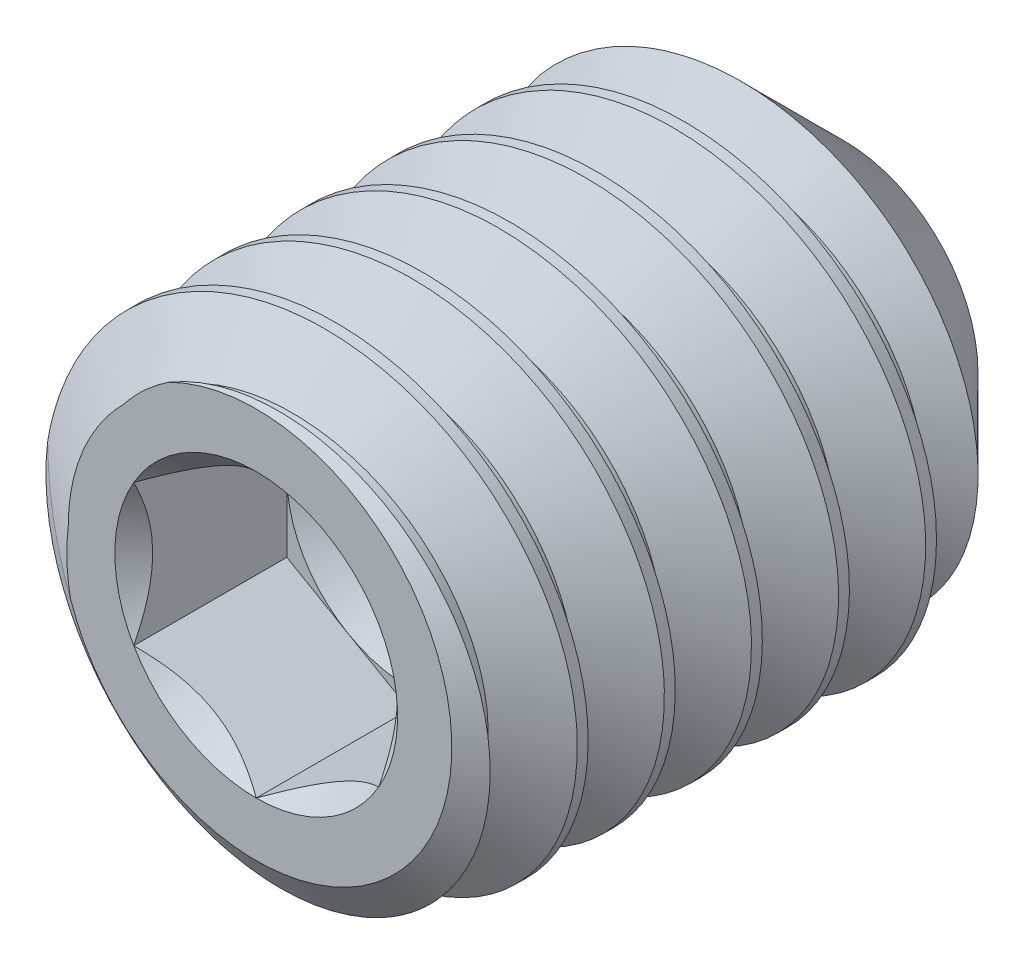
SolidWorks part; units mm, degrees
ref_plane "Front" through (0, 0, 0) normal (0, 0, 1) x (1, 0, 0)
ref_plane "Top" through (0, 0, 0) normal (0, 1, 0) x (1, 0, 0)
ref_plane "Right" through (0, 0, 0) normal (1, 0, 0) x (0, 0, -1)
sketch "Sketch22" plane through (0, 0, 0) normal (1, 0, 0) x (0, 0, -1)
  line L0 (-4.1102, 0) -> (-4.1102, 3.1699)
  line L1 (-4.1102, 3.1699) -> (-3.5553, 3.9624)
  line L2 (-3.5553, 3.9624) -> (3.6237, 3.9624)
  line L3 (3.6237, 3.9624) -> (5.4148, 2.1713)
  line L4 (5.4148, 2.1713) -> (4.1102, 0)
  line L5 (4.1102, 0) -> (-4.1102, 0)
  line L6 (4.1102, 0) -> (5.4148, 0) construction
  line L7 (5.4148, 0) -> (5.4148, 2.1713) construction
  line L8 (5.4148, -2.1713) -> (4.1102, 0) construction
  line L9 (-3.5553, -3.9624) -> (3.6237, -3.9624) construction
  dimension "Dia" = 7.9248
  dimension "Length" = 9.525
  dimension "D3" = 35
  dimension "D5" = 118
  dimension "D6" = 45
  dimension "D7" = 6.3398
revolve "Revolve1" add sketch "Sketch22" angle 360 about L6
ref_plane "Plane1" through (0, 0, -5.4148) normal (0, 0, 1) x (1, 0, 0)
sketch "Sketch27" plane through (0, 0, -5.4148) normal (0, 0, 1) x (1, 0, 0)
  circle A0 centre (0, 0) radius 3.9624 construction
  circle A1 centre (0, 0) radius 3.9624
curve "Helix/Spiral1" pitch 1.4111 height 10.9361 radius 3.9624 centre (0, 0, -5.4148) axis (0, 0, 1) start towards (0, 1, 0)
sketch "Sketch28" plane through (0, 0, 0) normal (1, 0, 0) x (0, 0, -1)
  line L0 (5.4148, 3.9624) -> (6.6495, 3.9624)
  line L1 (6.6495, 3.9624) -> (6.1204, 3.0459)
  line L2 (6.1204, 3.0459) -> (5.944, 3.0459)
  line L3 (5.944, 3.0459) -> (5.4148, 3.9624)
  line L4 (5.6794, 3.5041) -> (6.385, 3.5041) construction
  line L6 (-3.5553, 3.9624) -> (3.6237, 3.9624) construction
  line L7 (5.4148, 4.3586) -> (5.4148, -4.3586) construction
  dimension "D1" = 0.1764
  dimension "D3" = 60
  dimension "D2" = 0.7056
sweep "Cut-Sweep2" cut profiles "Sketch28" path "Helix/Spiral1" align with end faces yes
sketch "Sketch23" plane through (0, 0, 4.1102) normal (0, 0, 1) x (1, 0, 0)
  line L1 (0, 2.2914) -> (-1.9844, 1.1457)
  line L2 (-1.9844, 1.1457) -> (-1.9844, -1.1457)
  line L3 (-1.9844, -1.1457) -> (0, -2.2914)
  line L4 (0, -2.2914) -> (1.9844, -1.1457)
  line L5 (1.9844, -1.1457) -> (1.9844, 1.1457)
  line L6 (1.9844, 1.1457) -> (0, 2.2914)
  circle A0 centre (0, 0) radius 1.9844 construction
  dimension "Hex" = 3.9688
extrude "Cut-Extrude10" cut sketch "Sketch23" against normal blind 2.4805
sketch "Sketch24" plane through (0, 0, 4.1102) normal (0, 0, 1) x (1, 0, 0)
  circle A0 centre (0, 0) radius 2.2914
extrude "Cut-Extrude11" cut sketch "Sketch24" against normal through all draft 45
sketch "Sketch26" plane through (0, 0, 1.6297) normal (0, 0, 1) x (1, 0, 0)
  circle A0 centre (0, 0) radius 1.9844 construction
  circle A1 centre (0, 0) radius 1.9844
extrude "Cut-Extrude12" cut sketch "Sketch26" against normal through all draft 60
sketch "Sketch30" plane through (0, 0, 0) normal (1, 0, 0) x (0, 0, -1)
  line L0 (-3.5553, 3.9624) -> (3.6237, 3.9624) construction
  line L1 (-4.1102, 0) -> (-4.1102, 3.1699) construction
  line L2 (5.4148, 0) -> (5.4148, 2.1713) construction
  line L3 (-3.5553, -3.9624) -> (3.6237, -3.9624) construction
  point P0 (-4.1102, 3.9624)
  point P1 (5.4148, 3.9624)
  point P2 (5.4148, -3.9624)
  point P11 (0.4759, -3.9624)
  dimension "D1" = 4.9389
sketch "Sketch31" plane through (0, 0, 0) normal (1, 0, 0) x (0, 0, -1)
  line L2 (4.1102, 0) -> (5.4148, -2.1713)
  line L3 (5.4148, 2.1713) -> (4.1102, 0)
equation "\"D7@Sketch22\"=\"Dia@Sketch22\"*.8"
equation "\"D1@Sketch28\" = \"D4@Helix/Spiral1\" * .125"
equation "\"D3@Helix/Spiral1\" = \"Length@Sketch22\" + \"D4@Helix/Spiral1\""
equation "\"D1@Sketch30\" = \"D4@Helix/Spiral1\" * 3.5"
equation "\"hex Depth@Cut-Extrude10\" = \"Hex@Sketch23\" * .625"
equation "\"D2@Sketch28\" = \"D4@Helix/Spiral1\" * .5"
